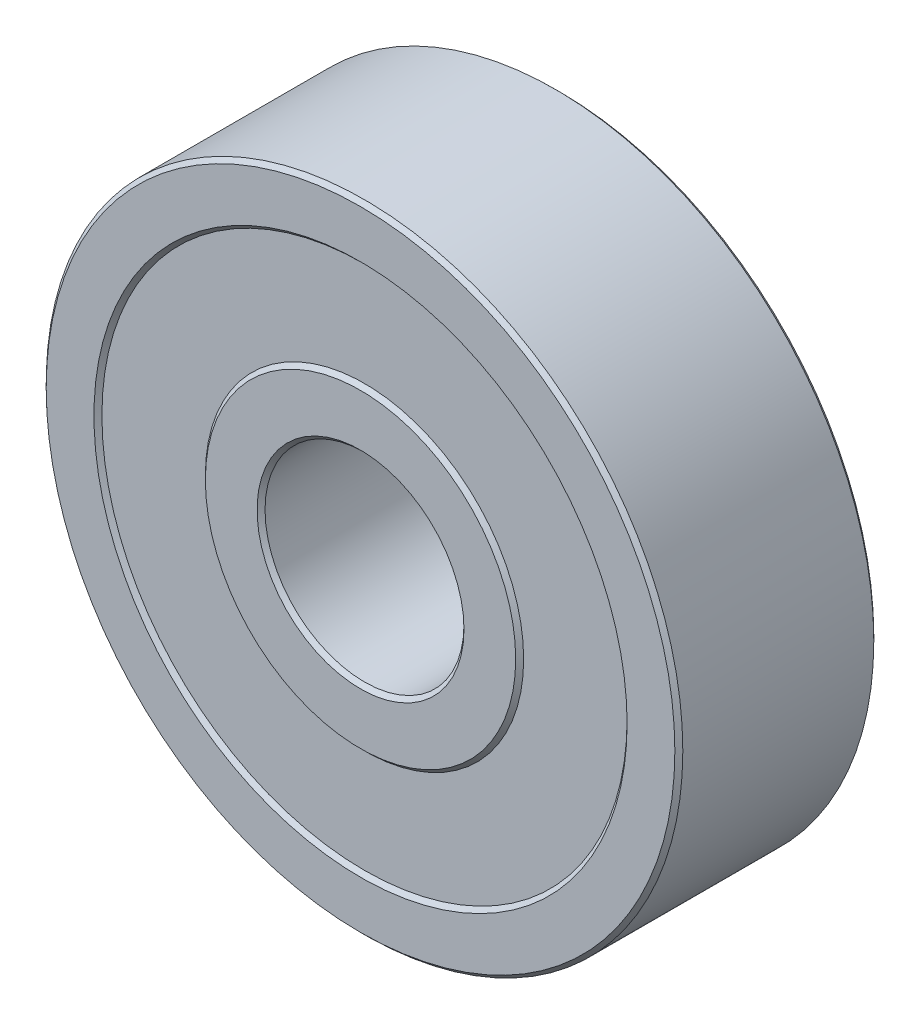
SolidWorks part; units mm, degrees
ref_plane "Front" through (0, 0, 0) normal (0, 0, 1) x (1, 0, 0)
ref_plane "Top" through (0, 0, 0) normal (0, 1, 0) x (1, 0, 0)
ref_plane "Right" through (0, 0, 0) normal (1, 0, 0) x (0, 0, -1)
sketch "Skizze1" plane through (0, 0, 0) normal (0, 0, 1) x (1, 0, 0)
  circle A0 centre (0, 0) radius 8
  circle A1 centre (0, 0) radius 2.5
  dimension "D1" = 16
  dimension "D2" = 5
extrude "Aufsatz-Linear austragen1" add sketch "Skizze1" along normal mid plane 5
sketch "Sketch1" plane through (0, 0, 0) normal (0, 1, 0) x (1, 0, 0)
  line L0 (0, 2.5) -> (0, -2.5) construction
  line L1 (2.5, 2.5) -> (-2.5, 2.5) construction
  line L2 (-8, -2.5) -> (8, -2.5) construction
  line L3 (6.6, 2.5) -> (6.6, 2.4)
  line L4 (8, 2.5) -> (-8, 2.5) construction
  line L5 (6.6, 2.4) -> (4, 2.4)
  line L6 (4, 2.4) -> (4, 2.5)
  line L7 (4, 2.5) -> (6.6, 2.5)
  line L8 (8, -2.5) -> (8, 2.5) construction
  line L9 (0, 0) -> (8, 0) construction
  line L10 (4, -2.5) -> (6.6, -2.5)
  line L11 (4, -2.4) -> (4, -2.5)
  line L12 (6.6, -2.4) -> (4, -2.4)
  line L13 (6.6, -2.5) -> (6.6, -2.4)
  dimension "D1" = 1.4
  dimension "D2" = 4
  dimension "D3" = 0.1
revolve "Cut-Revolve1" cut sketch "Sketch1" angle 360 about L0
chamfer "Chamfer1" distance 0.1 angle 45 8 edges at (-6.6, 0, 2.5) (-4, 0, 2.5) (8, 0, -2.5) (8, 0, 2.5) (2.5, 0, -2.5) (2.5, 0, 2.5) (-4, 0, -2.5) (-6.6, 0, -2.5)
